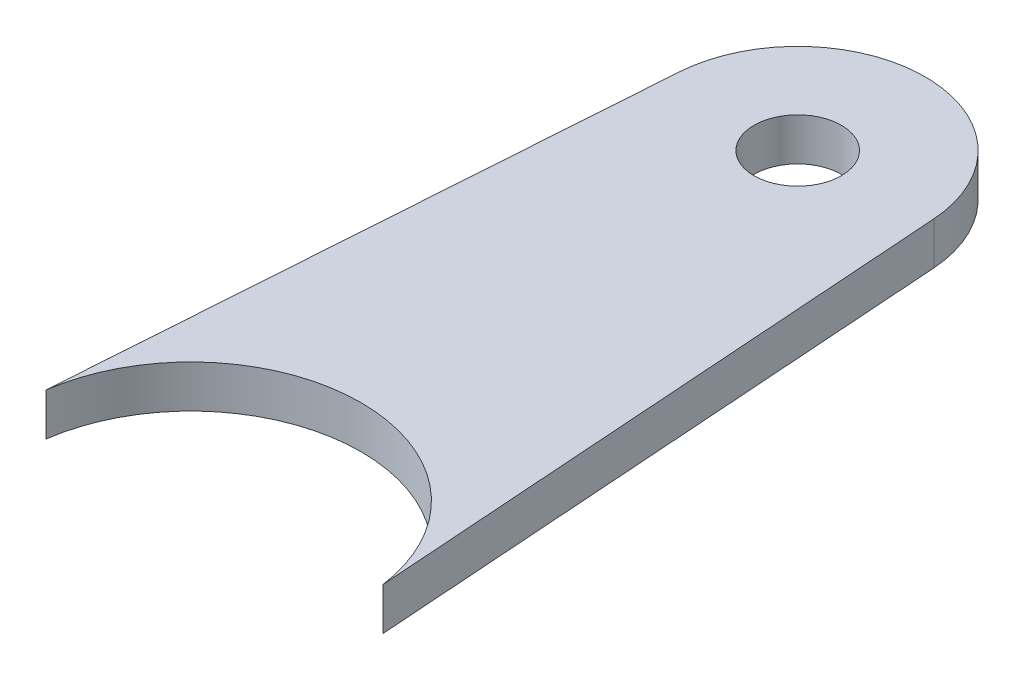
SolidWorks part; units mm, degrees
ref_plane "Front Plane" through (0, 0, 0) normal (0, 0, 1) x (1, 0, 0)
ref_plane "Top Plane" through (0, 0, 0) normal (0, 1, 0) x (1, 0, 0)
ref_plane "Right Plane" through (0, 0, 0) normal (1, 0, 0) x (0, 0, -1)
sketch "Sketch1" plane through (0, 0, 0) normal (0, 1, 0) x (1, 0, 0)
  line L0 (0, 0) -> (3.198, 45.9645)
  line L1 (0, 0) -> (25.4, 0)
  line L2 (25.4, 0) -> (22.202, 45.9645)
  line L3 (12.7, 42.0395) -> (12.7, 0) construction
  arc A1 (3.198, 45.9645) -> (22.202, 45.9645) centre (12.7, 45.3034) cw
  circle A2 centre (12.7, 45.3034) radius 3.2639
  circle A3 centre (12.7, 0) radius 12.7
  point P9 (12.7, 0)
  dimension "D1" = 6.5278
  dimension "D2" = 45.3034
  dimension "D3" = 9.525
  dimension "D5" = 25.4
  dimension "D4" = 25.4
extrude "Boss-Extrude1" add sketch "Sketch1" along normal blind 3.175 contours A3 L2 A1 L0 A2 region at (12.7, 0, -29.9923)
